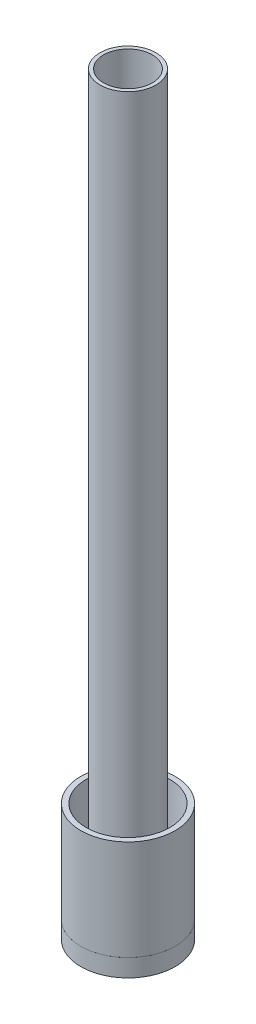
SolidWorks part; units mm, degrees
ref_plane "Front Plane" through (0, 0, 0) normal (0, 0, 1) x (1, 0, 0)
ref_plane "Top Plane" through (0, 0, 0) normal (0, 1, 0) x (1, 0, 0)
ref_plane "Right Plane" through (0, 0, 0) normal (1, 0, 0) x (0, 0, -1)
sketch "Sketch1" plane through (0, 0, 0) normal (0, 1, 0) x (1, 0, 0)
  circle A0 centre (0, 0) radius 26.2509
  circle A1 centre (0, 0) radius 30.1625
  circle A2 centre (0, 0) radius 45.0596
  circle A3 centre (0, 0) radius 50.8
  dimension "D1" = 52.5018
  dimension "D2" = 60.325
  dimension "D3" = 90.1192
  dimension "D4" = 101.6
extrude "Boss-Extrude1" add sketch "Sketch1" along normal blind 762 contours A0 | A1
extrude "Boss-Extrude2" add sketch "Sketch1<4>" along normal blind 76.2 and the other way blind 31.75 contours A3 | A2
sketch "Sketch1<4>" plane through (0, 0, 0) normal (0, 1, 0) x (1, 0, 0) same geometry as "Sketch1"
sketch "Sketch2" plane through (0, 0, 0) normal (0, 0, 1) x (1, 0, 0)
  line L0 (44.9096, -31.75) -> (50.8, -31.75)
  line L5 (44.7596, 0) -> (0, 0)
  line L7 (44.7596, -12.7) -> (0, -12.7)
  line L8 (0, 0) -> (0, -12.7)
  line L9 (44.7596, 0) -> (44.7596, -1.8747)
  line L10 (44.7596, -1.8747) -> (43.8616, -2.7727)
  line L11 (43.8616, -2.7727) -> (44.7596, -3.6708)
  line L12 (44.7596, -3.6708) -> (44.7596, -9.0292)
  line L13 (44.7596, -12.7) -> (44.7596, -10.8253)
  line L14 (44.7596, -9.0292) -> (43.8616, -9.9273)
  line L15 (43.8616, -9.9273) -> (44.7596, -10.8253)
  line L16 (45.0596, 17.3871) -> (45.0596, -20.2259) construction
  line L17 (-45.0596, -31.75) -> (45.0596, -31.75) construction
  line L18 (50.8, -31.75) -> (50.8, -50.8)
  line L19 (50.8, -50.8) -> (3.175, -50.8)
  line L21 (5.207, -19.05) -> (44.9096, -19.05)
  line L22 (44.9096, -19.05) -> (44.9096, -31.75)
  line L29 (5.207, -19.05) -> (5.207, -22.86)
  line L30 (5.207, -22.86) -> (3.175, -26.67)
  line L31 (3.175, -26.67) -> (3.175, -50.8)
  line L32 (0, 0) -> (0, -45.9457) construction
  point P15 (45.0596, 0)
  point P21 (3.175, -32.406)
  point P28 (3.175, -44.45)
  dimension "D6" = 12.7
  dimension "D1" = 12.7
  dimension "D2" = 1.27
  dimension "D3" = 0.15
  dimension "D4" = 1.8747
  dimension "D5" = 0.3
  dimension "D7" = 19.05
  dimension "D8" = 6.35
  dimension "D9" = 10.414
  dimension "D10" = 3.81
  dimension "D11" = 3.81
revolve "Revolve1" add sketch "Sketch2" angle 360 about L32 region at (26.0792, -35.53, 0) region at (22.317, -6.35, 0)
sketch "Sketch3" plane through (0, -50.8, 0) normal (0, -1, 0) x (1, 0, 0)
  line L0 (0, 0) -> (-25.4, 0) construction
  line L1 (-25.4, 15.24) -> (-25.4, -15.24) construction
  line L2 (-21.59, 15.24) -> (-21.59, 6.5991)
  line L3 (-29.21, 15.24) -> (-29.21, 6.5991)
  line L4 (-21.59, -6.5991) -> (-21.59, -15.24)
  line L5 (-29.21, -6.5991) -> (-29.21, -15.24)
  circle A0 centre (-25.4, 0) radius 7.62
  circle A1 centre (-25.4, 15.24) radius 3.81
  circle A2 centre (-25.4, -15.24) radius 3.81
  dimension "D1" = 15.24
  dimension "D3" = 7.62
  dimension "D4" = 3.81
  dimension "D2" = 25.4
extrude "Cut-Extrude1" cut sketch "Sketch3" against normal offset from surface (28.575 mm away) 3.175 contours A0 up to face at (-44.9096, -19.05, 0)
extrude "Cut-Extrude2" cut sketch "Sketch3<4>" against normal up to surface (31.75 mm away) from offset 9.525 contours A1 | A2 region at (-25.4, -50.8, 15.24) region at (-25.4, -50.8, -15.24) up to face at (-44.9096, -19.05, 0) offset against normal yes
sketch "Sketch3<4>" plane through (0, -50.8, 0) normal (0, -1, 0) x (1, 0, 0) same geometry as "Sketch3"
extrude "Cut-Extrude3" cut sketch "Sketch3<5>" against normal blind 6.35 from offset 9.525 contours A1 L3 A0 L2 | A2 L4 A0 L5 region at (-25.4, -50.8, 9.8323) region at (-25.4, -50.8, -9.8323) offset against normal yes
sketch "Sketch3<5>" plane through (0, -50.8, 0) normal (0, -1, 0) x (1, 0, 0) same geometry as "Sketch3"
sketch "Sketch4" plane through (0, 0, 0) normal (0, 0, 1) x (1, 0, 0)
  line L0 (-25.4, -67.051) -> (-25.4, 24.6353) construction
  line L1 (-21.59, -41.275) -> (-29.21, -41.275) construction
  line L2 (-22.86, -50.8) -> (-22.86, -44.069)
  line L3 (-22.86, -44.069) -> (-18.2562, -44.069)
  line L4 (-18.2562, -44.069) -> (-18.2562, -32.131)
  line L5 (-18.2562, -32.131) -> (-25.4, -32.131)
  line L6 (-18.2562, -38.1) -> (-25.4, -38.1) construction
  line L7 (-29.21, -34.925) -> (-21.59, -34.925) construction
  line L9 (-22.86, -60.706) -> (-25.4, -60.706)
  line L10 (-25.4, -60.706) -> (-25.4, -32.131)
  line L11 (-33.02, -50.8) -> (-17.78, -50.8) construction
  line L12 (-22.86, -50.8) -> (-22.86, -60.706)
  line L13 (-17.78, -32.131) -> (-17.78, -22.225) construction
  arc A0 (-18.2562, -32.6073) -> (-18.2562, -34.1948) centre (-18.2563, -33.401) ccw
  arc A1 (-18.2562, -43.5928) -> (-18.2562, -42.0052) centre (-18.2563, -42.799) cw
  dimension "D2" = 1.5875
  dimension "D3" = 12.7
  dimension "D4" = 2.794
  dimension "D1" = 2.794
  dimension "D5" = 1.27
  dimension "D6" = 5.08
revolve "Revolve2" add sketch "Sketch4" angle 360 about L0 region at (-22.6538, -42.9085, 0)
